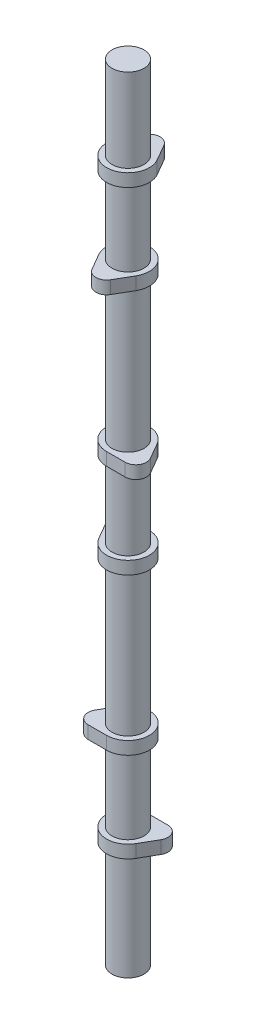
SolidWorks part; units mm, degrees
ref_plane "Front Plane" through (0, 0, 0) normal (0, 0, 1) x (1, 0, 0)
ref_plane "Top Plane" through (0, 0, 0) normal (0, 1, 0) x (1, 0, 0)
ref_plane "Right Plane" through (0, 0, 0) normal (1, 0, 0) x (0, 0, -1)
sketch "Sketch1" plane through (0, 0, 0) normal (0, 1, 0) x (1, 0, 0)
  line L0 (-5.4993, 15.875) -> (-10.9985, 6.35)
  line L1 (5.4993, 15.875) -> (10.9985, 6.35)
  arc A0 (-10.9985, 6.35) -> (10.9985, 6.35) centre (0, 0) ccw
  arc A1 (5.4993, 15.875) -> (-5.4993, 15.875) centre (0, 12.7) ccw
  dimension "D2" = 12.7
  dimension "D3" = 25.4
  dimension "D1" = 12.7
extrude "Boss-Extrude1" add sketch "Sketch1" along normal blind 7.62
ref_axis "Axis1" through (0, 22.5868, 0) along (0, -1, 0)
pattern_linear "LPattern2" count 2 spacing 53.34 along (0, -1, 0) of bodies 101
move or copy body "Body-Move/Copy1" bodies to move or copy 102 copy no rotation origin (0, 0, 0) rotation axis (0, 1, 0) rotation angle 180
pattern_linear "LPattern3" count 3 spacing 146.05 along (0, -1, 0) of bodies 101 103
move or copy body "Body-Move/Copy2" bodies to move or copy 104 106 copy no rotation origin (0, 0, 0) rotation axis (0, -1, 0) rotation angle 120
move or copy body "Body-Move/Copy3" bodies to move or copy 105 107 copy no rotation origin (0, 0, 0) rotation axis (0, 1, 0) rotation angle 120
sketch "Sketch2" plane through (0, 0, 0) normal (0, 1, 0) x (1, 0, 0)
  circle A0 centre (0, 0) radius 9.5
  dimension "D1" = 19
sketch "Sketch3" plane through (0, 7.62, 0) normal (0, 1, 0) x (1, 0, 0)
  circle A0 centre (0, 0) radius 9.5
extrude "Boss-Extrude2" add sketch "Sketch3" against normal blind 466.09 from offset 49.53
